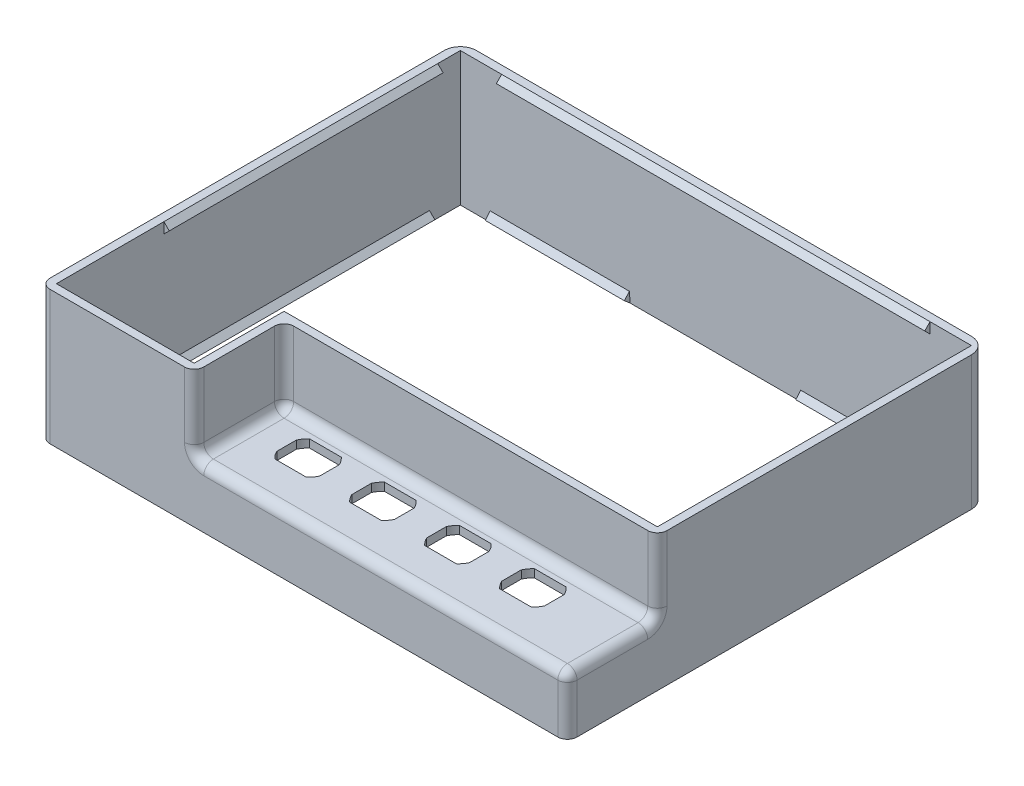
SolidWorks part; units mm, degrees
ref_plane "Front Plane" through (0, 0, 0) normal (0, 0, 1) x (1, 0, 0)
ref_plane "Top Plane" through (0, 0, 0) normal (0, 1, 0) x (1, 0, 0)
ref_plane "Right Plane" through (0, 0, 0) normal (1, 0, 0) x (0, 0, -1)
sketch "Sketch1" plane through (0, 0, 0) normal (0, 1, 0) x (1, 0, 0)
  line L0 (-47.72, -37.72) -> (-47.72, 37.72)
  line L1 (-49.22, -39.22) -> (49.22, -39.22)
  line L2 (-49.22, -39.22) -> (-49.22, 39.22)
  line L3 (-49.22, 39.22) -> (49.22, 39.22)
  line L4 (49.22, -39.22) -> (49.22, 39.22)
  line L5 (-49.22, -39.22) -> (49.22, 39.22) construction
  line L6 (-49.22, 39.22) -> (49.22, -39.22) construction
  line L7 (-47.72, 37.72) -> (47.72, 37.72)
  line L8 (47.72, -37.72) -> (47.72, 37.72)
  line L9 (-47.72, -37.72) -> (47.72, -37.72)
  line L16 (-20, -35.92) -> (45, -35.92) construction
  line L17 (-20, -35.92) -> (-20, 16.08) construction
  line L22 (-20, 16.08) -> (45, 16.08) construction
  line L23 (45, -35.92) -> (45, 16.08) construction
  point P0 (0, 0)
  point P10 (0, 0)
  dimension "D1" = 98.44
  dimension "D2" = 78.44
  dimension "D4" = 52
  dimension "D5" = 65
  dimension "D6" = 3.3
  dimension "D7" = 4.22
  dimension "D3" = 1.5
extrude "Boss-Extrude1" add sketch "Sketch1" along normal blind 25
ref_plane "Plane1" through (0, 11, 0) normal (0, -1, 0) x (-1, 0, 0)
sketch "Sketch3" plane through (0, 11, 0) normal (0, -1, 0) x (-1, 0, 0)
  line L1 (-34.9335, -25.17) -> (-29.0102, -25.17)
  line L2 (-35.9719, -26.5942) -> (-35.9719, -30.2458)
  line L3 (-34.9335, -31.67) -> (-29.0102, -31.67)
  line L4 (-27.9719, -26.5942) -> (-27.9719, -30.2458)
  line L5 (-20.9335, -25.17) -> (-15.0102, -25.17)
  line L6 (-21.9719, -26.5942) -> (-21.9719, -30.2458)
  line L18 (-13.9719, -26.5942) -> (-13.9719, -30.2458)
  line L19 (47.72, -37.72) -> (-47.72, -37.72) construction
  line L20 (-20.9335, -31.67) -> (-15.0102, -31.67)
  line L21 (-6.9335, -25.17) -> (-1.0102, -25.17)
  line L22 (-7.9719, -26.5942) -> (-7.9719, -30.2458)
  line L23 (0.0281, -26.5942) -> (0.0281, -30.2458)
  line L24 (-6.9335, -31.67) -> (-1.0102, -31.67)
  line L25 (7.0665, -25.17) -> (12.9898, -25.17)
  line L26 (6.0281, -26.5942) -> (6.0281, -30.2458)
  line L27 (14.0281, -26.5942) -> (14.0281, -30.2458)
  line L28 (7.0665, -31.67) -> (12.9898, -31.67)
  arc A0 (-34.9335, -25.17) -> (-35.9719, -26.5942) centre (-31.9719, -28.42) ccw
  arc A1 (-35.9719, -30.2458) -> (-34.9335, -31.67) centre (-31.9719, -28.42) ccw
  arc A2 (-29.0102, -31.67) -> (-27.9719, -30.2458) centre (-31.9719, -28.42) ccw
  arc A3 (-27.9719, -26.5942) -> (-29.0102, -25.17) centre (-31.9719, -28.42) ccw
  arc A4 (-20.9335, -25.17) -> (-21.9719, -26.5942) centre (-17.9719, -28.42) ccw
  arc A5 (-21.9719, -30.2458) -> (-20.9335, -31.67) centre (-17.9719, -28.42) ccw
  arc A6 (-13.9719, -26.5942) -> (-15.0102, -25.17) centre (-17.9719, -28.42) ccw
  arc A7 (-15.0102, -31.67) -> (-13.9719, -30.2458) centre (-17.9719, -28.42) ccw
  arc A8 (-6.9335, -25.17) -> (-7.9719, -26.5942) centre (-3.9719, -28.42) ccw
  arc A9 (-7.9719, -30.2458) -> (-6.9335, -31.67) centre (-3.9719, -28.42) ccw
  arc A10 (0.0281, -26.5942) -> (-1.0102, -25.17) centre (-3.9719, -28.42) ccw
  arc A11 (-1.0102, -31.67) -> (0.0281, -30.2458) centre (-3.9719, -28.42) ccw
  arc A12 (7.0665, -25.17) -> (6.0281, -26.5942) centre (10.0281, -28.42) ccw
  arc A13 (6.0281, -30.2458) -> (7.0665, -31.67) centre (10.0281, -28.42) ccw
  arc A14 (14.0281, -26.5942) -> (12.9898, -25.17) centre (10.0281, -28.42) ccw
  arc A15 (12.9898, -31.67) -> (14.0281, -30.2458) centre (10.0281, -28.42) ccw
  dimension "D1" = 9.3
  dimension "D2" = 8
  dimension "D3" = 6.5
  dimension "D4" = 4
sketch "Sketch4" plane through (0, 11, 0) normal (0, -1, 0) x (-1, 0, 0)
  line L0 (49.22, 39.22) -> (49.22, -39.22) construction
  line L1 (49.22, -39.22) -> (-49.22, -39.22)
  line L2 (49.22, -39.22) -> (49.22, -22.42)
  line L3 (49.22, -22.42) -> (-49.22, -22.42)
  line L4 (-49.22, -39.22) -> (-49.22, -22.42)
  line L5 (49.22, -39.22) -> (-49.22, -39.22) construction
  line L6 (-49.22, -39.22) -> (-49.22, 39.22) construction
  dimension "D1" = 6
extrude "Boss-Extrude2" add sketch "Sketch4" along normal blind 1.5
extrude "Cut-Extrude1" cut sketch "Sketch3" along normal blind 1.6
sketch "Sketch5" plane through (49.22, 0, 0) normal (1, 0, 0) x (0, 0, -1)
  line L0 (-32.736, 11) -> (32.736, 11) construction
  line L1 (-39.22, 25) -> (-21.22, 25)
  line L2 (-39.22, 25) -> (-39.22, 11)
  line L3 (-39.22, 11) -> (-21.22, 11)
  line L4 (-21.22, 25) -> (-21.22, 11)
  dimension "D1" = 18
extrude "Cut-Extrude2" cut sketch "Sketch5" against normal blind 70.5
sketch "Sketch7" plane through (0, 0, 0) normal (1, 0, 0) x (0, 0, -1)
  line L1 (-22.42, 25) -> (-20.92, 25)
  line L2 (-22.42, 25) -> (-22.42, 9.5)
  line L3 (-22.42, 9.5) -> (-20.92, 9.5)
  line L4 (-20.92, 25) -> (-20.92, 9.5)
  dimension "D1" = 1.5
  dimension "D2" = 15.5
extrude "Boss-Extrude9" add sketch "Sketch7" along normal blind 49.22 and the other way blind 22
ref_plane "Plane2" through (0, 0, 24.04) normal (0, 0, 1) x (1, 0, 0)
sketch "Sketch9" plane through (0, 0, 24.04) normal (0, 0, 1) x (1, 0, 0)
  line L0 (-47.72, 2) -> (-46.72, 1)
  line L1 (-46.72, 1) -> (-47.72, 0)
  line L2 (-47.72, 0) -> (-47.72, 2)
  dimension "D1" = 2
extrude "Boss-Extrude10" add sketch "Sketch9" against normal blind 56 and the other way blind 8
mirror "Mirror1" about plane through (0, 0, 0) normal (1, 0, 0) of "Boss-Extrude10"
sketch "Sketch10" plane through (0, 0, 0) normal (1, 0, 0) x (0, 0, -1)
  line L1 (-37.72, 0) -> (-36.5609, -0.8102)
  line L2 (-36.5609, -0.8102) -> (-35.7507, 0.349)
  line L3 (-35.7507, 0.349) -> (-37.72, 0)
  dimension "D1" = 2
extrude "Boss-Extrude11" add sketch "Sketch10" along normal blind 42 and the other way blind 42 separate body
extrude "Cut-Extrude3" cut sketch "Sketch10<2>" against normal blind 16 and the other way blind 16
sketch "Sketch10<2>" plane through (0, 0, 0) normal (1, 0, 0) x (0, 0, -1) same geometry as "Sketch10"
sketch "Sketch11" plane through (0, 0, 0) normal (1, 0, 0) x (0, 0, -1)
  line L0 (37.559, 2) -> (36.6395, 0.9195)
  line L1 (36.6395, 0.9195) -> (37.72, 0)
  line L2 (37.72, 0) -> (37.559, 2)
  dimension "D1" = 2
extrude "Boss-Extrude12" add sketch "Sketch11" along normal blind 42 and the other way blind 42 separate body
extrude "Cut-Extrude4" cut sketch "Sketch11<2>" against normal blind 16 and the other way blind 16
sketch "Sketch11<2>" plane through (0, 0, 0) normal (1, 0, 0) x (0, 0, -1) same geometry as "Sketch11"
sketch "Sketch12" plane through (0, 0, 0) normal (1, 0, 0) x (0, 0, -1)
  line L0 (36.72, 24) -> (37.72, 25)
  line L1 (37.72, 25) -> (37.72, 23)
  line L2 (37.72, 23) -> (36.72, 24)
  dimension "D1" = 2
extrude "Boss-Extrude13" add sketch "Sketch12" along normal blind 40 and the other way blind 40
ref_plane "Plane3" through (0, 0, -17.86) normal (0, 0, 1) x (1, 0, 0)
sketch "Sketch14" plane through (0, 0, -17.86) normal (0, 0, 1) x (1, 0, 0)
  line L0 (47.72, 25) -> (46.72, 24)
  line L1 (46.72, 24) -> (47.72, 23)
  line L2 (47.72, 23) -> (47.72, 25)
  dimension "D1" = 2
extrude "Boss-Extrude14" add sketch "Sketch14" along normal blind 35.5 and the other way blind 15.64
mirror "Mirror3" about plane through (0, 0, 0) normal (1, 0, 0) of "Boss-Extrude14"
fillet "Fillet4" radius 1.8 5 edges at (49.22, 18, 22.42) (-49.22, 12.5, 39.22) (49.22, 5.5, 39.22) (49.22, 11, 30.82) (13.61, 11, 22.42)
sketch "Sketch16" plane through (0, 0, 22.42) normal (0, 0, 1) x (1, 0, 0)
  line L1 (-22, 25) -> (-20.5, 25)
  line L2 (-22, 25) -> (-22, 11)
  line L3 (-22, 11) -> (-20.5, 11)
  line L4 (-20.5, 25) -> (-20.5, 11)
  dimension "D1" = 1.5
extrude "Boss-Extrude15" add sketch "Sketch16" along normal blind 16.8 contours L2 L1 L4 L3
sketch "Sketch17" plane through (-47.72, 0, 0) normal (1, 0, 0) x (0, 0, -1)
  line L1 (-37.72, 11) -> (-22.42, 11)
  line L2 (-37.72, 11) -> (-37.72, 9.5)
  line L3 (-37.72, 9.5) -> (-22.42, 9.5)
  line L4 (-22.42, 11) -> (-22.42, 9.5)
extrude "Cut-Extrude6" cut sketch "Sketch17" along normal blind 25.72
fillet "Fillet5" radius 1.8 6 edges at (-20.5, 11, 31.72) (-20.5, 11.5272, 22.9472) (-20.5, 18.9, 22.42) (48.6928, 10.4728, 38.6928) (13.46, 11, 39.22) (-20.5, 18, 39.22)
ref_plane "Plane13" through (40.72, 0, 0) normal (-1, 0, 0) x (0, 0, 1)
sketch "Sketch19" plane through (40.72, 0, 0) normal (-1, 0, 0) x (0, 0, 1)
  line L0 (20.92, 25) -> (19.92, 24)
  line L1 (19.92, 24) -> (20.92, 23)
  line L2 (20.92, 23) -> (20.92, 25)
  dimension "D1" = 2
extrude "Boss-Extrude16" add sketch "Sketch19" along normal blind 53
fillet "Fillet6" radius 3 2 edges at (49.22, 12.5, -39.22) (-49.22, 12.5, -39.22)
